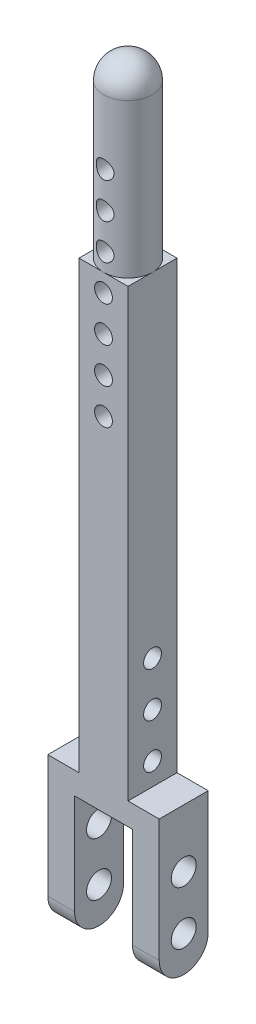
SolidWorks part; units mm, degrees
ref_plane "Front Plane" through (0, 0, 0) normal (0, 0, 1) x (1, 0, 0)
ref_plane "Top Plane" through (0, 0, 0) normal (0, 1, 0) x (1, 0, 0)
ref_plane "Right Plane" through (0, 0, 0) normal (1, 0, 0) x (0, 0, -1)
sketch "Sketch1" plane through (0, 0, 0) normal (0, 0, 1) x (1, 0, 0)
  line L0 (-6.25, -1.202) -> (-6.25, -17.702)
  line L1 (-3.25, -3.702) -> (3.25, -3.702)
  line L2 (-3.25, -17.702) -> (-6.25, -17.702)
  line L3 (-2.75, 48.798) -> (2.75, 48.798)
  line L4 (2.75, -1.202) -> (2.75, 48.798)
  line L5 (2.75, -1.202) -> (6.25, -1.202)
  line L6 (3.25, -3.702) -> (3.25, -17.702)
  line L7 (3.25, -17.702) -> (6.25, -17.702)
  line L8 (6.25, -1.202) -> (6.25, -17.702)
  line L9 (-3.25, -3.702) -> (-3.25, -17.702)
  line L10 (-2.75, -1.202) -> (-6.25, -1.202)
  line L11 (-2.75, -1.202) -> (-2.75, 48.798)
  point P15 (0, -3.702)
  dimension "D1" = 3
  dimension "D2" = 50
  dimension "D3" = 2.5
  dimension "D4" = 3
  dimension "D5" = 14
  dimension "D6" = 3.25
  dimension "D7" = 0.5
  dimension "D8" = 0.5
  dimension "D9" = 14
  dimension "D10" = 2.5
extrude "Boss-Extrude1" add sketch "Sketch1" along normal blind 5.5
sketch "Sketch2" plane through (2.75, 0, 0) normal (1, 0, 0) x (0, 0, -1)
  line L0 (-5.5, -1.202) -> (0, -1.202) construction
  line L1 (-5.5, -1.202) -> (-5.5, 48.798) construction
  circle A0 centre (-2.75, 1.298) radius 1
  circle A1 centre (-2.75, 6.298) radius 1
  circle A2 centre (-2.75, 11.298) radius 1
  dimension "D2" = 2
  dimension "D8" = 2
  dimension "D9" = 2
  dimension "D1" = 2.5
  dimension "D3" = 2.75
  dimension "D4" = 0
  dimension "D5" = 5
  dimension "D6" = 0
  dimension "D7" = 5
extrude "Cut-Extrude1" cut sketch "Sketch2" against normal blind 5.5
sketch "Sketch3" plane through (6.25, 0, 0) normal (1, 0, 0) x (0, 0, -1)
  line L0 (0, -17.702) -> (0, -1.202) construction
  line L1 (-5.5, -3.702) -> (0, -3.702) construction
  circle A0 centre (-2.75, -7.702) radius 1.4
  circle A1 centre (-2.75, -13.702) radius 1.4
  dimension "D5" = 2.8
  dimension "D6" = 2.8
  dimension "D1" = 2.75
  dimension "D2" = 2.75
  dimension "D3" = 6
  dimension "D4" = 4
extrude "Cut-Extrude2" cut sketch "Sketch3" against normal blind 20
sketch "Sketch4" plane through (0, 48.798, 0) normal (0, 1, 0) x (1, 0, 0)
  line L0 (-2.75, -5.5) -> (-2.75, 0) construction
  line L1 (2.75, 0) -> (-2.75, 0) construction
  circle A0 centre (0, -2.75) radius 2.75
  dimension "D3" = 5.5
  dimension "D1" = 2.75
  dimension "D2" = 2.75
extrude "Boss-Extrude2" add sketch "Sketch4" along normal blind 20
fillet "Fillet1" radius 2.75 1 edges at (0, 68.798, 5.5)
sketch "Sketch5" plane through (0, 0, 0) normal (0, 0, -1) x (-1, 0, 0)
  line L0 (0, 48.798) -> (2.75, 48.798) construction
  line L1 (2.75, 48.798) -> (2.75, -1.202) construction
  circle A0 centre (0, 52.798) radius 0.9
  circle A1 centre (0, 57.798) radius 0.9
  dimension "D1" = 1.8
  dimension "D3" = 1.8
  dimension "D2" = 4
  dimension "D4" = 5
  dimension "D5" = 2.75
  dimension "D6" = 0
fillet "Fillet2" radius 2.75 4 edges at (4.75, -17.702, 5.5) (4.75, -17.702, 0) (-4.75, -17.702, 0) (-4.75, -17.702, 5.5)
sketch "Sketch6" plane through (0, 0, 0) normal (0, 0, -1) x (-1, 0, 0)
  line L0 (-2.75, -1.202) -> (-2.75, 48.798) construction
  line L1 (2.75, -1.202) -> (6.25, -1.202) construction
  circle A0 centre (0, 46.798) radius 1
  circle A1 centre (0, 42.798) radius 1
  circle A2 centre (0, 38.798) radius 1
  circle A3 centre (0, 34.798) radius 1
  circle A4 centre (0, 50.798) radius 1
  circle A5 centre (0, 54.798) radius 1
  circle A6 centre (0, 58.798) radius 1
  dimension "D1" = 2
  dimension "D4" = 2
  dimension "D5" = 2
  dimension "D6" = 2
  dimension "D13" = 2
  dimension "D14" = 2
  dimension "D15" = 2
  dimension "D2" = 2.75
  dimension "D3" = 48
  dimension "D7" = 4
  dimension "D8" = 4
  dimension "D9" = 4
  dimension "D10" = 2.75
  dimension "D11" = 2.75
  dimension "D12" = 2.75
  dimension "D16" = 4
  dimension "D17" = 4
  dimension "D18" = 4
  dimension "D19" = 2.75
  dimension "D20" = 2.75
  dimension "D21" = 2.75
extrude "Cut-Extrude4" cut sketch "Sketch6" against normal blind 10
